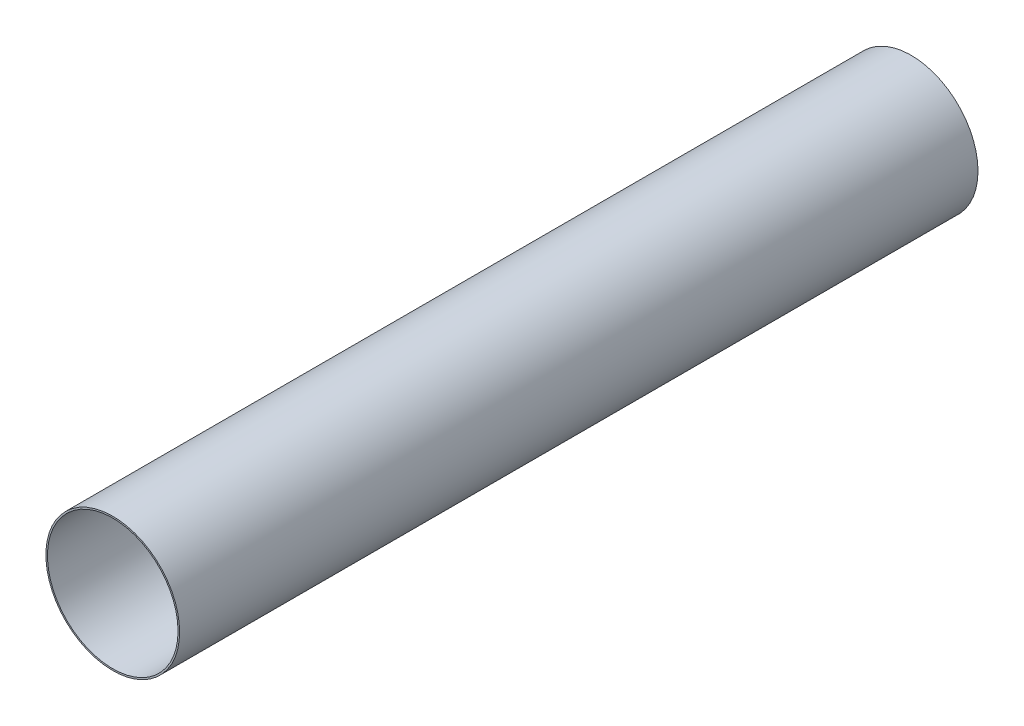
SolidWorks part; units mm, degrees
material "Thornel Mat VMA"
ref_plane "Front Plane" through (0, 0, 0) normal (0, 0, 1) x (1, 0, 0)
ref_plane "Top Plane" through (0, 0, 0) normal (0, 1, 0) x (1, 0, 0)
ref_plane "Right Plane" through (0, 0, 0) normal (1, 0, 0) x (0, 0, -1)
sketch "Sketch1" plane through (0, 0, 0) normal (0, 0, 1) x (1, 0, 0)
  circle A0 centre (0, 0) radius 85.0999
  circle A1 centre (0, 0) radius 83.0999
  dimension "D1" = 166.1998
  dimension "D2" = 170.1998
extrude "Boss-Extrude1" add sketch "Sketch1" along normal mid plane 1016
equation "\"TubeDiameter\" = 6.5433in"
equation "\"D1@Sketch1\"=\"TubeDiameter\""
equation "\"D2@Sketch1\"=\"TubeDiameter\"+4mm"
